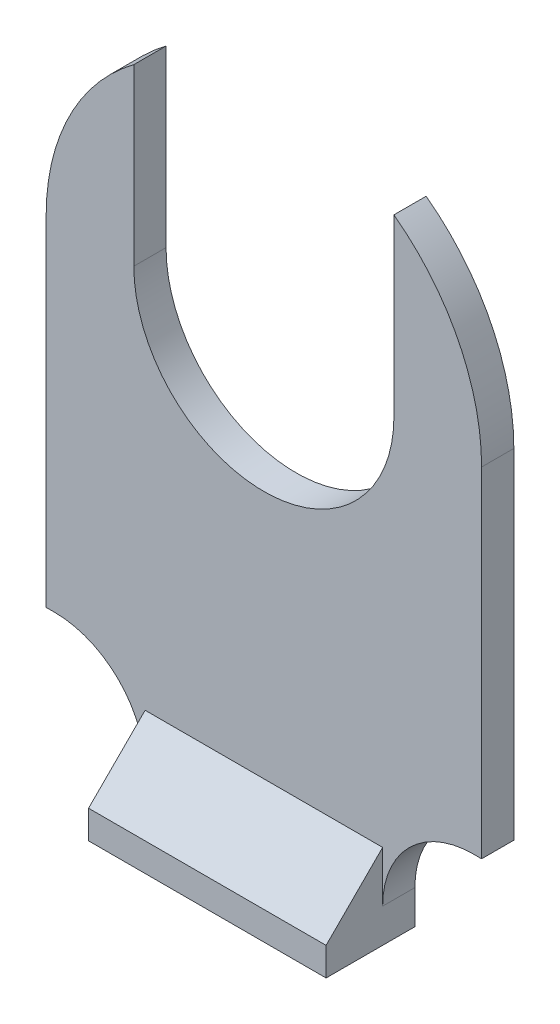
SolidWorks part; units mm, degrees
ref_plane "Спереди" through (0, 0, 0) normal (0, 0, 1) x (1, 0, 0)
ref_plane "Сверху" through (0, 0, 0) normal (0, 1, 0) x (1, 0, 0)
ref_plane "Справа" through (0, 0, 0) normal (1, 0, 0) x (0, 0, -1)
sketch "Эскиз1" plane through (0, 0, 0) normal (0, 0, 1) x (1, 0, 0)
  line L0 (-4.6, 0) -> (-4.6, 6.1749)
  line L1 (7.7, -20.6) -> (-7.7, -20.6)
  line L2 (7.7, -20.6) -> (7.7, 0)
  line L3 (4.6, 0) -> (4.6, 6.1749)
  line L4 (-7.7, -20.6) -> (-7.7, 0)
  arc A0 (7.7, 0) -> (4.6, 6.1749) centre (0, 0) ccw
  arc A1 (-4.6, 0) -> (4.6, 0) centre (0, 0) ccw
  arc A2 (-4.6, 6.1749) -> (-7.7, 0) centre (0, 0) ccw
  point P0 (0, 0)
  point P3 (0, -20.6)
  dimension "D3" = 9.2
  dimension "D1" = 20.6
  dimension "D2" = 15.4
extrude "Бобышка-Вытянуть1" add sketch "Эскиз1" along normal blind 1.24
sketch "Эскиз3" plane through (0, 0, 1.24) normal (0, 0, 1) x (1, 0, 0)
  line L0 (0, 0) -> (0, -20.6) construction
  line L1 (-7.7, -20.6) -> (-4.2, -20.6)
  line L2 (-7.7, -20.6) -> (-7.7, -12)
  line L3 (-7.7, -12) -> (-7.4, -12)
  line L4 (-4.2, -20.6) -> (-4.2, -15.2)
  line L5 (-7.7, -20.6) -> (7.7, -20.6) construction
  line L6 (4.2, -20.6) -> (4.2, -15.2)
  line L7 (7.7, -12) -> (7.4, -12)
  line L8 (7.7, -20.6) -> (7.7, -12)
  line L9 (7.7, -20.6) -> (4.2, -20.6)
  arc A0 (-4.2, -15.2) -> (-7.4, -12) centre (-7.4, -15.2) ccw
  arc A1 (4.2, -15.2) -> (7.4, -12) centre (7.4, -15.2) cw
  dimension "D3" = 3.2
  dimension "D1" = 4.2
  dimension "D2" = 8.6
extrude "Вырез-Вытянуть1" cut sketch "Эскиз3" against normal up to surface (1.24 mm away) up to face at (0, -4.0895, 0)
sketch "Эскиз4" plane through (0, 0, 1.24) normal (0, 0, 1) x (1, 0, 0)
  line L0 (4.2, -15.2) -> (4.2, -20.6) construction
  line L1 (-4.2, -20.6) -> (4.2, -20.6)
  line L2 (-4.2, -20.6) -> (-4.2, -17.6)
  line L3 (-4.2, -17.6) -> (4.2, -17.6)
  line L4 (4.2, -20.6) -> (4.2, -17.6)
  dimension "D1" = 3
extrude "Бобышка-Вытянуть2" add sketch "Эскиз4" along normal blind 2.2
chamfer "Фаска1" distance 1.2 distance2 2.4 1 edges at (0, -17.6, 1.24) first distance on face at (0, -7.4136, 1.24)
sketch "Эскиз5" plane through (0, 0, 3.44) normal (0, 0, 1) x (1, 0, 0)
  line L1 (-4.2, -20.6) -> (4.2, -20.6)
  line L2 (-4.2, -20.6) -> (-4.2, -16.4)
  line L3 (-4.2, -16.4) -> (4.2, -16.4)
  line L4 (4.2, -20.6) -> (4.2, -16.4)
extrude "Вырез-Вытянуть2" cut sketch "Эскиз5" against normal through all
sketch "Эскиз6" plane through (0, 0, 1.24) normal (0, 0, 1) x (1, 0, 0)
  line L1 (4.2, -16.4) -> (-4.2, -16.4)
  line L2 (4.2, -16.4) -> (4.2, -13.4)
  line L3 (4.2, -13.4) -> (-4.2, -13.4)
  line L4 (-4.2, -16.4) -> (-4.2, -13.4)
  dimension "D1" = 3
extrude "Бобышка-Вытянуть3" add sketch "Эскиз6" along normal blind 2
chamfer "Фаска2" distance 2 angle 45 1 edges at (0, -13.4, 3.24)
sketch "Эскиз7" plane through (0, 0, 0) normal (0, 0, -1) x (-1, 0, 0)
  line L9 (-4.2, -15.2) -> (-4.2, -16.4)
  line L10 (-4.2, -16.4) -> (4.2, -16.4)
  line L11 (4.2, -16.4) -> (4.2, -15.2)
  line L12 (7.4, -12) -> (7.7, -12)
  line L13 (7.7, -12) -> (7.7, 0)
  line L14 (4.6, 6.1749) -> (4.6, 0)
  line L15 (-4.6, 0) -> (-4.6, 6.1749)
  line L16 (-7.7, 0) -> (-7.7, -12)
  line L17 (-7.7, -12) -> (-7.4, -12)
  line L18 (-4.2, -15.2) -> (-4.2, -16.4)
  line L19 (-4.2, -16.4) -> (4.2, -16.4)
  line L20 (4.2, -16.4) -> (4.2, -15.2)
  line L21 (7.4, -12) -> (7.7, -12)
  line L22 (7.7, -12) -> (7.7, 0)
  line L23 (4.6, 6.1749) -> (4.6, 0)
  line L24 (-4.6, 0) -> (-4.6, 6.1749)
  line L25 (-7.7, 0) -> (-7.7, -12)
  line L26 (-7.7, -12) -> (-7.4, -12)
  arc A5 (7.4, -12) -> (4.2, -15.2) centre (7.4, -15.2) ccw
  arc A6 (7.7, 0) -> (4.6, 6.1749) centre (0, 0) ccw
  arc A7 (-4.6, 0) -> (4.6, 0) centre (0, 0) ccw
  arc A8 (-4.6, 6.1749) -> (-7.7, 0) centre (0, 0) ccw
  arc A9 (-4.2, -15.2) -> (-7.4, -12) centre (-7.4, -15.2) ccw
  arc A10 (7.4, -12) -> (4.2, -15.2) centre (7.4, -15.2) ccw
  arc A11 (7.7, 0) -> (4.6, 6.1749) centre (0, 0) ccw
  arc A12 (-4.6, 0) -> (4.6, 0) centre (0, 0) ccw
  arc A13 (-4.6, 6.1749) -> (-7.7, 0) centre (0, 0) ccw
  arc A14 (-4.2, -15.2) -> (-7.4, -12) centre (-7.4, -15.2) ccw
  dimension "D1" = 0
extrude "Вырез-Вытянуть3" cut sketch "Эскиз7" against normal blind 0.1
